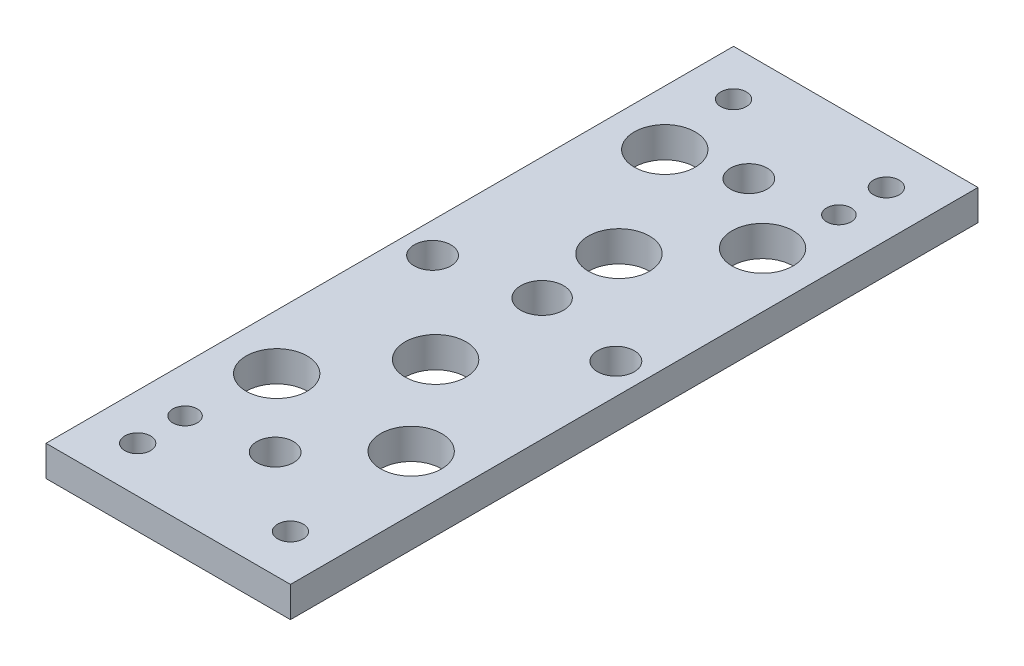
SolidWorks part; units mm, degrees
material "K110"
ref_plane "Front Plane" through (0, 0, 0) normal (0, 0, 1) x (1, 0, 0)
ref_plane "Top Plane" through (0, 0, 0) normal (0, 1, 0) x (1, 0, 0)
ref_plane "Right Plane" through (0, 0, 0) normal (1, 0, 0) x (0, 0, -1)
sketch "Sketch1" plane through (0, 0, 0) normal (0, 1, 0) x (1, 0, 0)
  line L1 (-40, -112.5) -> (40, -112.5)
  line L2 (-40, -112.5) -> (-40, 112.5)
  line L3 (-40, 112.5) -> (40, 112.5)
  line L4 (40, -112.5) -> (40, 112.5)
  line L5 (-40, -112.5) -> (40, 112.5) construction
  line L6 (-40, 112.5) -> (40, -112.5) construction
  point P0 (0, 0)
  dimension "D1" = 225
  dimension "D2" = 80
extrude "Boss-Extrude1" add sketch "Sketch1" against normal blind 10
sketch "Sketch2" plane through (0, 0, 0) normal (0, 1, 0) x (1, 0, 0)
  circle A0 centre (0, 77.5) radius 6 construction
  circle A1 centre (30, 4) radius 6 construction
  circle A2 centre (-30, 4) radius 6 construction
  circle A3 centre (0, -77.5) radius 6 construction
  circle A4 centre (0, 77.5) radius 6
  circle A5 centre (30, 4) radius 6
  circle A6 centre (-30, 4) radius 6
  circle A7 centre (0, -77.5) radius 6
extrude "Cut-Extrude1" cut sketch "Sketch2" against normal up to next
hole_wizard "M8 Clearance Hole1" positions "Sketch6" profile "Sketch5" hole size "M8" standard "ISO" end condition through all
sketch "Sketch6" plane through (0, 0, 0) normal (0, 1, 0) x (1, 0, 0)
  point P0 (-25, 97.5)
  point P3 (25, 97.5)
  point P6 (25, -97.5)
  point P9 (-25, -97.5)
sketch "Sketch5" plane through (-25, 0, -97.5) normal (1, 0, 0) x (0, 0, 1)
  line L0 (0, 0) -> (0, 10)
  line L1 (0, 10) -> (4.2, 10)
  line L2 (4.2, 10) -> (4.2, 0)
  line L5 (4.2, 0) -> (0, 0)
  line L11 (0, -6.35) -> (0, 107.95) construction
  dimension "Thru Hole Dia." = 8.4
  dimension "Thru Hole Depth" = 10
hole_wizard "Ø8.0mm Dowel Hole1" positions "Sketch9" profile "Sketch8" hole size "Ø8.0" standard "ISO" end condition through all
sketch "Sketch9" plane through (0, 0, 0) normal (0, 1, 0) x (1, 0, 0)
  point P0 (25, 81.975)
  point P3 (-25, -82)
sketch "Sketch8" plane through (25, 0, -81.975) normal (1, 0, 0) x (0, 0, 1)
  line L0 (0, 0) -> (0, 10)
  line L1 (0, 10) -> (4, 10)
  line L2 (4, 10) -> (4, 0)
  line L5 (4, 0) -> (0, 0)
  line L11 (0, -6.35) -> (0, 107.95) construction
  dimension "Thru Hole Dia." = 8
  dimension "Thru Hole Depth" = 10
sketch "Sketch10" plane through (0, 0, 0) normal (0, 1, 0) x (1, 0, 0)
  circle A0 centre (0, 9.86) radius 7 construction
  circle A1 centre (0, 9.86) radius 7
extrude "Cut-Extrude3" cut sketch "Sketch10" against normal up to next
sketch "Sketch14" plane through (0, -10, 0) normal (0, 1, 0) x (1, 0, 0)
  circle A0 centre (22, 60) radius 10 construction
  circle A1 centre (-22, 72) radius 10 construction
  circle A2 centre (0, 35) radius 10 construction
  circle A3 centre (0, -25) radius 10 construction
  circle A4 centre (-22, -55) radius 10 construction
  circle A5 centre (22, -55) radius 10 construction
  circle A6 centre (22, 60) radius 10
  circle A7 centre (-22, 72) radius 10
  circle A8 centre (0, 35) radius 10
  circle A9 centre (0, -25) radius 10
  circle A10 centre (-22, -55) radius 10
  circle A11 centre (22, -55) radius 10
extrude "Cut-Extrude4" cut sketch "Sketch14" along normal through all
